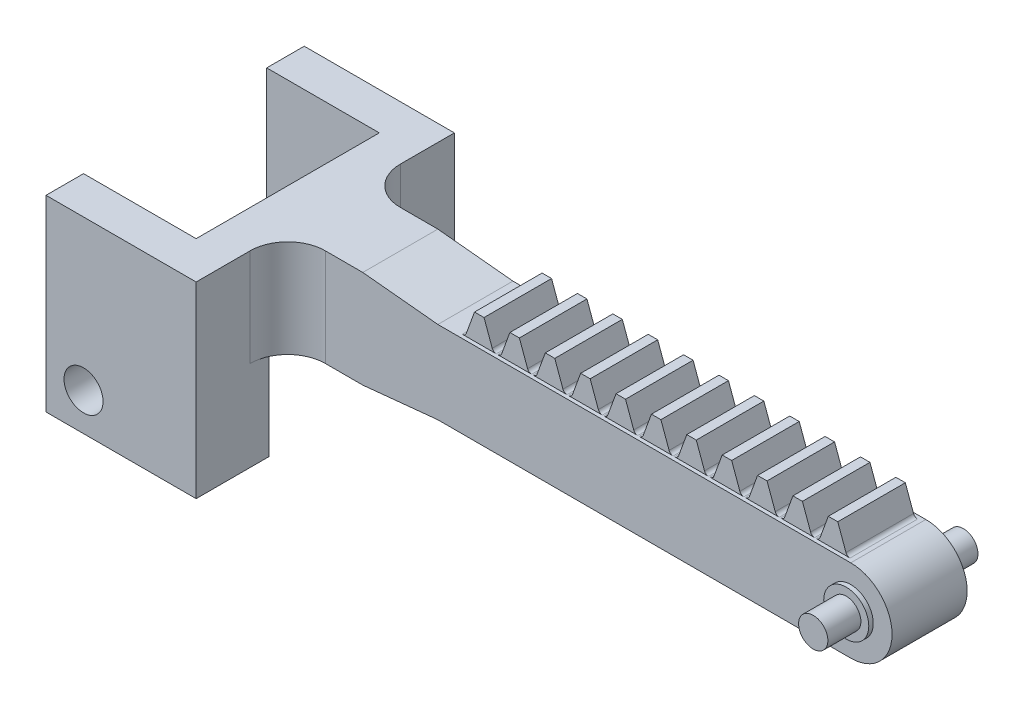
SolidWorks part; units mm, degrees
ref_plane "Front Plane" through (0, 0, 0) normal (0, 0, 1) x (1, 0, 0)
ref_plane "Top Plane" through (0, 0, 0) normal (0, 1, 0) x (1, 0, 0)
ref_plane "Right Plane" through (0, 0, 0) normal (1, 0, 0) x (0, 0, -1)
sketch "Esquisse1" plane through (0, 0, 0) normal (0, 0, 1) x (1, 0, 0)
  line L0 (-27.5, 5.5) -> (-37.5, 6.5)
  line L1 (-27.5, 5.5) -> (27.5, 5.5)
  line L2 (-37.5, 6.5) -> (-47.5, 6.5)
  line L3 (-27.5, -5.5) -> (27.5, -5.5)
  line L4 (-47.5, 6.5) -> (-47.5, -6.5)
  line L5 (-47.5, -6.5) -> (-37.5, -6.5)
  line L6 (-37.5, -6.5) -> (-27.5, -5.5)
  line L7 (55, 0) -> (-55, 0) construction
  arc A0 (27.5, 5.5) -> (27.5, -5.5) centre (27.5, 0) cw
  point P6 (0, -5.5)
  point P13 (-47.5, 0)
  dimension "D1" = 11
  dimension "D2" = 55
  dimension "D3" = 13
  dimension "D4" = 10
  dimension "D5" = 10
extrude "Main Extrusion" add sketch "Esquisse1" along normal mid plane 10
sketch "Esquisse2" plane through (0, 0, 0) normal (0, 0, 1) x (1, 0, 0)
  circle A0 centre (27.5, 0) radius 1.95
  arc A1 (27.5, -5.5) -> (27.5, 5.5) centre (27.5, 0) ccw construction
  dimension "D1" = 3.9
extrude "RollingBearFixing" add sketch "Esquisse2" along normal mid plane 20
sketch "Esquisse6" plane through (0, 0, 5) normal (0, 0, 1) x (1, 0, 0)
  circle A0 centre (27.5, 0) radius 3
  circle A1 centre (27.5, 0) radius 1.95 construction
  dimension "D1" = 6
extrude "RollingBearFixingSpacer" add sketch "Esquisse6" along normal blind 0.6
mirror "RollingBearFixingSpacer2" about plane through (0, 0, 0) normal (0, 0, 1) of "RollingBearFixingSpacer"
sketch "Esquisse5" plane through (0, 0, 0) normal (0, 0, 1) x (1, 0, 0)
  line L0 (22.7789, 5.5) -> (24.0073, 8.875)
  line L1 (24.0073, 8.875) -> (25.2716, 8.875)
  line L2 (25.2716, 8.875) -> (26.5, 5.5)
  line L3 (22.7789, 5.5) -> (21.7876, 5.5) construction
  line L4 (22.7789, 5.5) -> (26.5, 5.5)
  line L5 (27.5, 5.5) -> (-27.5, 5.5) construction
  line L6 (22.9154, 5.875) -> (21.6511, 5.875) construction
  line L7 (22.7789, 5.5) -> (22.7789, 8.8688) construction
  line L9 (21.7876, 5.5) -> (20.7594, 8.325) construction
  line L10 (21.1052, 7.375) -> (25.8176, 7.375) construction
  dimension "D1" = 20
  dimension "D2" = 1.5
  dimension "h" = 3.375
  dimension "p" = 4.7124
  dimension "hw" = 3
  dimension "D3" = 1
extrude "Tooth" add sketch "Esquisse5" along normal mid plane 9
fillet "Tooth Fillet" radius 0.57 2 edges at (22.7789, 5.5, 0) (26.5, 5.5, 0)
pattern_linear "ToothRepeat" count 11 spacing 4.7124 along (-1, 0, 0) of "Tooth Fillet", "Tooth"
sketch "Esquisse10" plane through (0, 6.5, 0) normal (0, 1, 0) x (1, 0, 0)
  line L0 (-47.5, -5) -> (-47.5, 5) construction
  line L1 (-47.5, -17.2) -> (-67.5, -17.2)
  line L2 (-67.5, -17.2) -> (-67.5, -12.2)
  line L3 (-67.5, -12.2) -> (-52.5, -12.2)
  line L4 (-52.5, -12.2) -> (-52.5, 12.2)
  line L5 (-52.5, 12.2) -> (-67.5, 12.2)
  line L6 (-67.5, 12.2) -> (-67.5, 17.2)
  line L7 (-67.5, 17.2) -> (-47.5, 17.2)
  line L8 (-47.5, 17.2) -> (-47.5, -17.2)
  point P14 (-47.5, 0)
  point P15 (-47.5, 0)
  dimension "D1" = 24.4
  dimension "D2" = 5
  dimension "D3" = 5
  dimension "D4" = 15
extrude "FixingSupport" add sketch "Esquisse10" against normal blind 25 separate body
sketch "Esquisse11" plane through (0, 0, 17.2) normal (0, 0, 1) x (1, 0, 0)
  line L0 (-67.5, -18.5) -> (-67.5, 6.5) construction
  line L2 (-67.5, -18.5) -> (-47.5, -18.5) construction
  circle A0 centre (-62.5, -13.5) radius 2.6
  dimension "D1" = 5.2
  dimension "D2" = 5
  dimension "D3" = 5
extrude "FixingHoles" cut sketch "Esquisse11" against normal through all
sketch "Esquisse12" plane through (-47.5, 0, 0) normal (1, 0, 0) x (0, 0, -1)
  line L0 (-17.2, -18.5) -> (17.2, -18.5) construction
  line L1 (7.5, -6.5) -> (-7.5, -6.5)
  line L2 (7.5, -6.5) -> (7.5, -18.5)
  line L3 (7.5, -18.5) -> (-7.5, -18.5)
  line L4 (-7.5, -6.5) -> (-7.5, -18.5)
  point P6 (-7.5, -6.3058)
  point P7 (0, -18.5)
  point P8 (0, -18.5)
  dimension "D1" = 15
  dimension "D2" = 12
extrude "RackHole" cut sketch "Esquisse12" against normal through all
sketch "Esquisse14" plane through (0, 6.5, 0) normal (0, 1, 0) x (1, 0, 0)
  line L0 (-47.5, -5) -> (-47.5, -10)
  line L1 (-47.5, -17.2) -> (-47.5, 17.2) construction
  line L2 (-37.5, -5) -> (-47.5, -5) construction
  line L3 (-47.5, -5) -> (-42.5, -5)
  arc A0 (-42.5, -5) -> (-47.5, -10) centre (-42.5, -10) ccw
  dimension "D1" = 5
extrude "Fillet" add sketch "Esquisse14" against normal up to surface (13 mm away) up to face at (-50, -6.5, 0)
mirror "FilletSymetry" about plane through (0, 0, 0) normal (0, 0, 1) of "Fillet"
equation "\"modulo\"= 1.5mm"
equation "\"h@Esquisse5\"= \"modulo\" * 2.25"
equation "\"D2@Esquisse5\"= \"modulo\""
equation "\"p@Esquisse5\"= \"modulo\" * pi"
equation "\"hw@Esquisse5\"= \"modulo\" * 2"
equation "\"0.5è\"=10"
